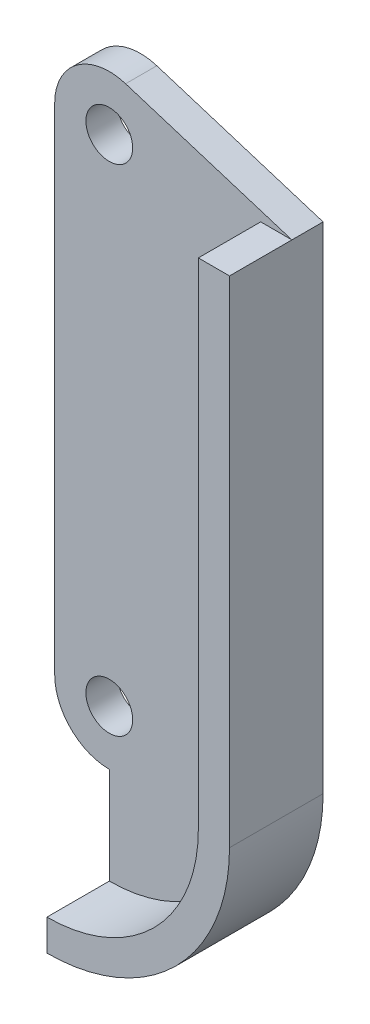
SolidWorks part; units mm, degrees
material "ABS"
ref_plane "Front Plane" through (0, 0, 0) normal (0, 0, 1) x (1, 0, 0)
ref_plane "Top Plane" through (0, 0, 0) normal (0, 1, 0) x (1, 0, 0)
ref_plane "Right Plane" through (0, 0, 0) normal (1, 0, 0) x (0, 0, -1)
sketch "Sketch1" plane through (0, 0, 0) normal (0, 0, 1) x (1, 0, 0)
  line L0 (0, 0) -> (0, 31.75) construction
  line L2 (11.7079, 0) -> (11.7079, 31.75)
  line L3 (0, 0) -> (0, 31.75) construction
  line L5 (9.7079, 0) -> (9.7079, 31.75)
  line L6 (0, -11.7079) -> (0, -9.7079)
  line L7 (0, -9.7079) -> (0, 0) construction
  line L8 (9.7079, 31.75) -> (11.7079, 31.75)
  line L9 (-3.5, 31.75) -> (-3.5, 0)
  line L10 (1.0463, 35.0899) -> (11.7079, 31.75)
  line L11 (0, -9.7079) -> (0, -3.5)
  line L12 (9.7079, 0) -> (11.7079, 0) construction
  circle A0 centre (0, 0) radius 1.5
  arc A2 (0, -11.7079) -> (11.7079, 0) centre (0, 0) ccw
  arc A4 (0, -9.7079) -> (9.7079, 0) centre (0, 0) ccw
  circle A6 centre (0, 31.75) radius 1.5
  circle A7 centre (0, 31.75) radius 3.5
  circle A8 centre (0, 0) radius 3.5
  point P4 (9.7079, 31.5699)
  dimension "D1" = 3
  dimension "D2" = 3
  dimension "D4" = 19.4158
  dimension "D5" = 2
  dimension "D8" = 7
  dimension "D3" = 31.75
  dimension "D6" = 180
  dimension "D7" = 31.75
  dimension "D9" = 2
extrude "Boss-Extrude1" add sketch "Sketch1" along normal blind 2 contours A8 L11 A4 L5 L8 L10 A7 L9 | A7 A6 | A8 A0 | A4 L6 A2 L2 L8 L5 region at (7.9605, -7.9605, 0) region at (3.6359, 13.4375, 0) region at (2.7409, 33.7636, 0) region at (-2.4049, -2.4049, 0)
extrude "Boss-Extrude2" add sketch "Sketch1<3>" along normal blind 4 from surface contours A4 L6 A2 L2 L8 L5 region at (7.9605, -7.9605, 0) starting at face at (2.6167, 11.6262, 2)
sketch "Sketch1<3>" plane through (0, 0, 0) normal (0, 0, 1) x (1, 0, 0) same geometry as "Sketch1"
